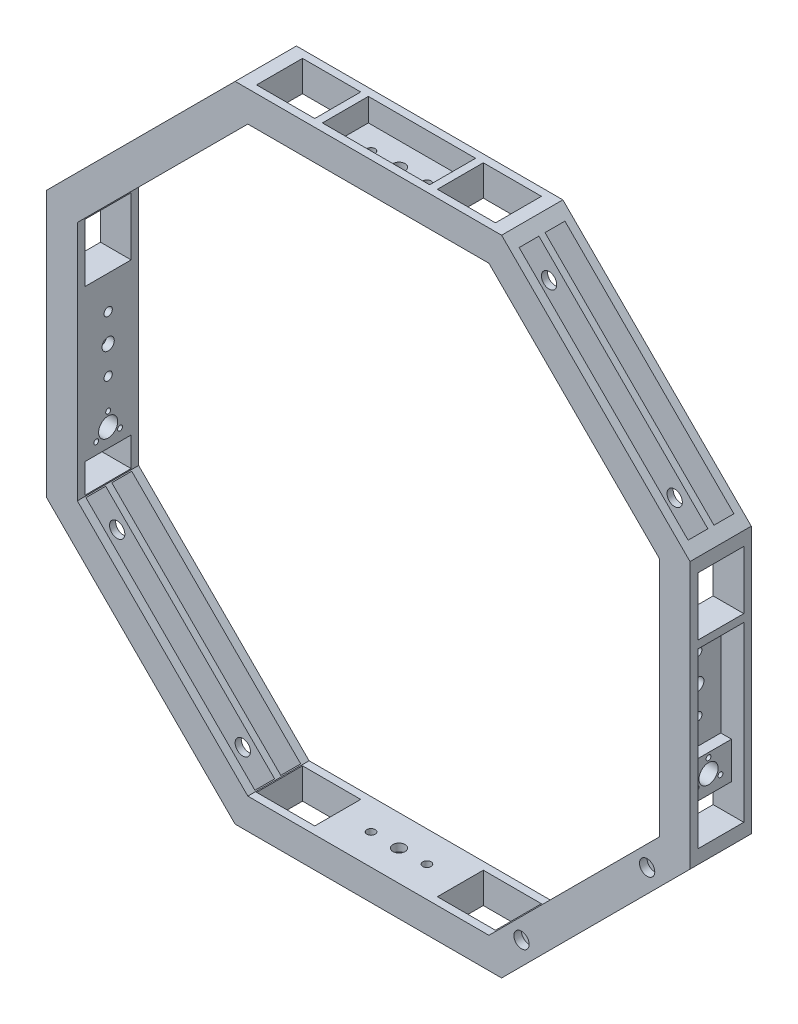
SolidWorks part; units mm, degrees
ref_plane "Plano frontal" through (0, 0, 0) normal (0, 0, 1) x (1, 0, 0)
ref_plane "Plano superior" through (0, 0, 0) normal (0, 1, 0) x (1, 0, 0)
ref_plane "Plano direito" through (0, 0, 0) normal (1, 0, 0) x (0, 0, -1)
sketch "Esboço1" plane through (0, 0, 0) normal (0, 0, 1) x (1, 0, 0)
  line L9 (210, 86.9848) -> (86.9848, 210)
  line L10 (86.9848, 210) -> (-86.9848, 210)
  line L11 (-86.9848, 210) -> (-210, 86.9848)
  line L12 (-210, 86.9848) -> (-210, -86.9848)
  line L13 (-210, -86.9848) -> (-86.9848, -210)
  line L14 (-86.9848, -210) -> (86.9848, -210)
  line L15 (86.9848, -210) -> (210, -86.9848)
  line L16 (210, -86.9848) -> (210, 86.9848)
  line L17 (190, 78.7006) -> (78.7006, 190)
  line L18 (78.7006, 190) -> (-78.7006, 190)
  line L19 (-78.7006, 190) -> (-190, 78.7006)
  line L20 (-190, 78.7006) -> (-190, -78.7006)
  line L21 (-190, -78.7006) -> (-78.7006, -190)
  line L22 (-78.7006, -190) -> (78.7006, -190)
  line L23 (78.7006, -190) -> (190, -78.7006)
  line L24 (190, -78.7006) -> (190, 78.7006)
  circle A0 centre (0, 0) radius 210 construction
  circle A1 centre (0, 0) radius 190 construction
extrude "Ressalto-extrusão1" add sketch "Esboço1" along normal blind 40
sketch "Esboço2" plane through (210, 0, 0) normal (1, 0, 0) x (0, 0, -1)
  line L1 (-4.9012, 78) -> (-4.9012, -78)
  line L23 (-4.9012, 78) -> (-34.9012, 78)
  line L24 (-34.9012, 78) -> (-34.9012, -78)
  line L25 (-4.9012, -78) -> (-34.9012, -78)
  line L26 (-4.9012, 78) -> (-4.9012, -78)
  line L27 (-4.9012, 78) -> (-34.9012, 78)
  line L28 (-34.9012, 78) -> (-34.9012, -78)
  line L29 (-4.9012, -78) -> (-34.9012, -78)
  line L30 (-4.9012, 0) -> (-4.9012, -59)
  line L31 (-34.9012, 0) -> (-34.9012, -59)
  line L32 (-4.9012, -59) -> (-34.9012, -59)
  line L33 (-4.9012, 0) -> (-4.9012, 40)
  line L34 (-34.9012, 0) -> (-34.9012, 40)
  line L35 (-4.9012, 40) -> (-34.9012, 40)
  line L36 (-4.9012, 35) -> (-4.9012, -35)
  line L37 (-4.9012, 35) -> (-34.9012, 35)
  line L38 (-34.9012, 35) -> (-34.9012, -35)
  line L39 (-4.9012, -35) -> (-34.9012, -35)
  circle A0 centre (-19.9012, 0) radius 4
  circle A1 centre (-19.9012, -18.25) radius 2.7
  circle A2 centre (-19.9012, 18.25) radius 2.7
  circle A8 centre (-19.9012, -38) radius 1.6
  circle A9 centre (-19.9012, -47) radius 6.25
  circle A10 centre (-12.107, -51.5) radius 1.6
  circle A11 centre (-27.6954, -51.5) radius 1.6
  point P30 (-19.9012, -47)
  dimension "D1" = 3
extrude "Corte-extrusão2" cut sketch "Esboço2" against normal up to next and the other way through all contours L1 L32 L24 L25 | A0 | A2 | A1 | L35 L1 L23 L24 region at (210, 59, 19.9012) region at (210, -68.5, 19.9012) region at (210, 0, 19.9012) region at (210, -18.25, 19.9012) region at (210, 18.25, 19.9012)
extrude "Corte-extrusão15" cut sketch "Esboço2<6>" against normal up to next contours A8 | A9 | A10 | A11 region at (210, -38, 19.9012) region at (210, -47, 19.9012) region at (210, -51.5, 12.107) region at (210, -51.5, 27.6954)
sketch "Esboço2<6>" plane through (210, 0, 0) normal (1, 0, 0) x (0, 0, -1) same geometry as "Esboço2"
extrude "Corte-extrusão16" cut sketch "Esboço2<7>" against normal blind 8 contours L30 L39 L31 L32 A11 A10 A9 A8 region at (210, -47, 5.2854)
sketch "Esboço2<7>" plane through (210, 0, 0) normal (1, 0, 0) x (0, 0, -1) same geometry as "Esboço2"
sketch "Esboço15" plane through (-148.4924, 148.4924, 0) normal (-0.7071, 0.7071, 0) x (0, 0, 1)
  line L0 (40, 86.9848) -> (0, 86.9848) construction
  line L1 (5, 86.9848) -> (35, 86.9848)
  line L2 (5, 86.9848) -> (5, -86.9848)
  line L3 (5, -86.9848) -> (35, -86.9848)
  line L4 (35, 86.9848) -> (35, -86.9848)
  line L5 (40, -86.9848) -> (0, -86.9848) construction
  line L9 (20, 86.9848) -> (22, 86.9848)
  line L11 (20, -86.9848) -> (22, -86.9848)
  line L12 (22, 78) -> (22, -78)
  line L14 (20, 86.9848) -> (18, 86.9848)
  line L16 (20, -86.9848) -> (18, -86.9848)
  line L17 (18, 78) -> (18, -78)
  line L19 (5, 86.9848) -> (35, 86.9848)
  line L20 (5, 86.9848) -> (5, 78)
  line L21 (5, 78) -> (35, 78)
  line L22 (35, 86.9848) -> (35, 78)
  line L24 (5, -86.9848) -> (35, -86.9848)
  line L25 (5, -86.9848) -> (5, -78)
  line L26 (5, -78) -> (35, -78)
  line L27 (35, -86.9848) -> (35, -78)
extrude "Corte-extrusão5" cut sketch "Esboço15" against normal up to next contours L12 L26 L4 L21 | L2 L26 L17 L21 region at (-148.4924, 148.4924, 11.5) region at (-148.4924, 148.4924, 28.5)
sketch "Esboço16" plane through (148.4924, 148.4924, 0) normal (0.7071, 0.7071, 0) x (0, 0, -1)
  line L0 (-40, 86.9848) -> (0, 86.9848) construction
  line L2 (-34.9012, -78) -> (-34.9012, 86.9848)
  line L3 (-34.9012, 86.9848) -> (-5, 86.9848)
  line L4 (-5, -86.8738) -> (-5, 86.9848)
  line L8 (-34.9012, -78) -> (-5, -78)
  line L9 (-5, -86.8738) -> (-5, -78)
  line L10 (-5, 86.9848) -> (-34.9012, 86.9848)
  line L11 (-5, 86.9848) -> (-5, 78)
  line L12 (-5, 78) -> (-34.9012, 78)
  line L13 (-34.9012, 86.9848) -> (-34.9012, 78)
  line L14 (-19.9506, 78) -> (-18, 78)
  line L16 (-20, -78) -> (-18, -78)
  line L17 (-18, 78) -> (-18, -78)
  line L18 (-20, -78) -> (-22, -78)
  line L20 (-19.9506, 78) -> (-22, 78)
  line L21 (-22, -78) -> (-22, 78)
  line L22 (-34.9012, -78) -> (-5, -78)
  line L23 (-34.9012, -78) -> (-34.9012, -86.8738)
  line L24 (-34.9012, -86.8738) -> (-5, -86.8738)
  line L25 (-5, -78) -> (-5, -86.8738)
extrude "Corte-extrusão6" cut sketch "Esboço16" against normal through all both and the other way through all contours L8 L21 L12 L2 | L12 L17 L8 L4 region at (148.4924, 148.4924, 28.4506) region at (148.4924, 148.4924, 11.5)
sketch "Esboço18" plane through (0, -210, 0) normal (0, -1, 0) x (1, 0, 0)
  line L1 (-78, 35) -> (78, 35)
  line L2 (-78, 35) -> (-78, 5)
  line L3 (-78, 5) -> (78, 5)
  line L4 (78, 35) -> (78, 5)
  line L5 (-78, 35) -> (78, 35)
  line L6 (-78, 35) -> (-78, 5)
  line L7 (-78, 5) -> (78, 5)
  line L8 (78, 35) -> (78, 5)
  line L9 (0, 35) -> (40.0505, 35)
  line L11 (0, 5) -> (40.0505, 5)
  line L12 (40.0505, 35) -> (40.0505, 5)
  line L13 (0, 35) -> (-40, 35)
  line L15 (0, 5) -> (-40, 5)
  line L16 (-40, 35) -> (-40, 5)
  line L17 (-35, 35) -> (35, 35)
  line L18 (-35, 35) -> (-35, 5)
  line L19 (-35, 5) -> (35, 5)
  line L20 (35, 35) -> (35, 5)
  circle A0 centre (0, 20) radius 4
  circle A1 centre (18.25, 20) radius 2.7
  circle A2 centre (-18.25, 20) radius 2.7
  line M8 (86.9848, 0) -> (86.9848, 40)
  line M12 (-86.9848, 40) -> (-86.9848, 0)
sketch "Esboço26" plane through (0, 0, 0) normal (0, 0, -1) x (-1, 0, 0)
  circle A0 centre (100, 182) radius 5
  circle A1 centre (182, 100) radius 5
  circle A2 centre (-182, -100) radius 5
  circle A3 centre (-100, -182) radius 5
  circle A4 centre (100, -182) radius 5
  circle A5 centre (182, -100) radius 5
  circle A6 centre (-182, 100) radius 5
  circle A7 centre (-100, 182) radius 5
extrude "Corte-extrusão10" cut sketch "Esboço26" against normal up to next from surface starting at face at (141.4214, 141.4214, 18)
extrude "Corte-extrusão12" cut sketch "Esboço18" against normal through all contours L16 L1 L3 M12 | L1 L12 L3 M8 | A2 | A0 | A1 region at (-59, -210, 20) region at (59.0253, -210, 20) region at (0, -210, 20) region at (18.25, -210, 20) region at (-18.25, -210, 20)
extrude "Corte-extrusão13" cut sketch "Esboço18<4>" against normal blind 15 contours L20 L5 L13 L18 L15 L7 A2 A1 A0 region at (-17.5, -210, 34.2384)
sketch "Esboço18<4>" plane through (0, -210, 0) normal (0, -1, 0) x (1, 0, 0) same geometry as "Esboço18"
extrude "Corte-extrusão14" cut sketch "Esboço2<5>" against normal blind 15 contours L39 L26 L33 L37 L34 L28 A2 A1 A0 region at (210, 17.5, 5.6628)
sketch "Esboço2<5>" plane through (210, 0, 0) normal (1, 0, 0) x (0, 0, -1) same geometry as "Esboço2"
mirror "Espelhar6" about plane through (0, 0, 0) normal (1, 0, 0) of "Corte-extrusão16", "Corte-extrusão15", "Corte-extrusão14", "Corte-extrusão2"
ref_plane "Plano1" through (0, 0, 0) normal (-0.7071, 0.7071, 0) x (0.7071, 0.7071, 0)
mirror "Espelhar8" about plane through (0, 0, 0) normal (-0.7071, 0.7071, 0) of "Corte-extrusão5"
mirror "Espelhar9" about plane through (0, 0, 0) normal (0, 1, 0) of "Corte-extrusão13", "Corte-extrusão12"
